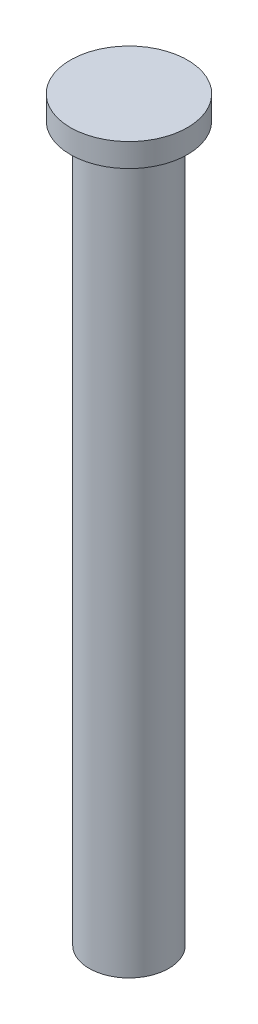
SolidWorks part; units mm, degrees
ref_plane "Plan de face" through (0, 0, 0) normal (0, 0, 1) x (1, 0, 0)
ref_plane "Plan de dessus" through (0, 0, 0) normal (0, 1, 0) x (1, 0, 0)
ref_plane "Plan de droite" through (0, 0, 0) normal (1, 0, 0) x (0, 0, -1)
sketch "Esquisse1" plane through (0, 0, 0) normal (0, 1, 0) x (1, 0, 0)
  circle A0 centre (0, 0) radius 3.4
  dimension "D1" = 6.8
extrude "Boss.-Extru.1" add sketch "Esquisse1" along normal blind 61
sketch "Esquisse3" plane through (0, 61, 0) normal (0, 1, 0) x (1, 0, 0)
  circle A0 centre (0, 0) radius 5
  dimension "D1" = 10
extrude "Boss.-Extru.2" add sketch "Esquisse3" along normal blind 2
